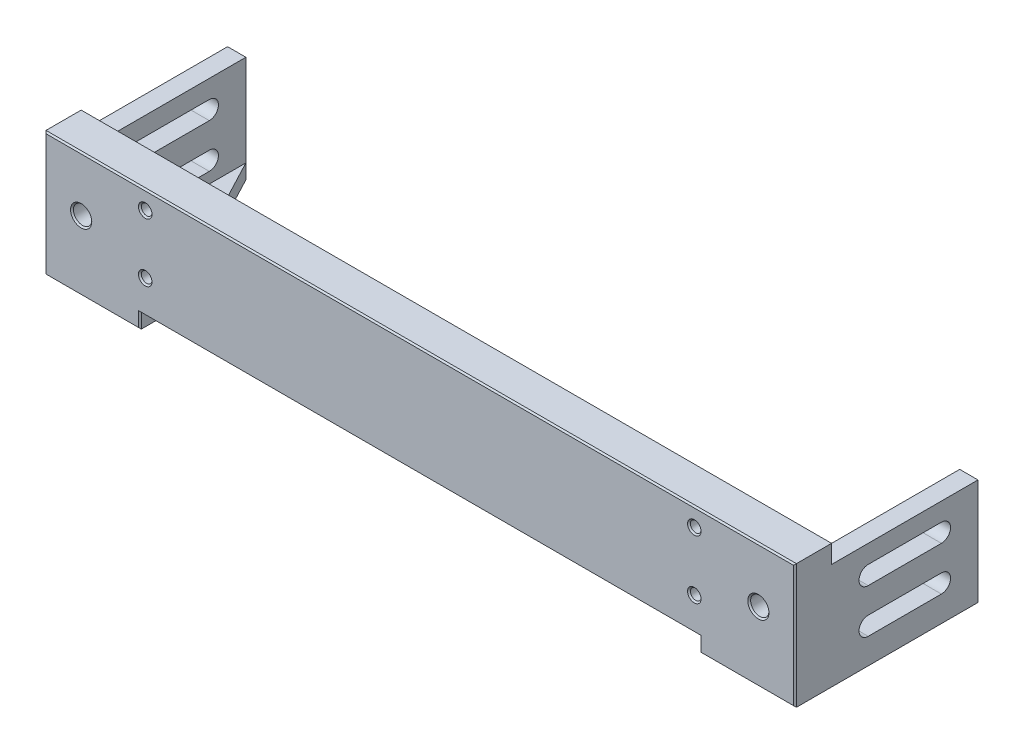
SolidWorks part; units mm, degrees
ref_plane "Front Plane" through (0, 0, 0) normal (0, 0, 1) x (1, 0, 0)
ref_plane "Top Plane" through (0, 0, 0) normal (0, 1, 0) x (1, 0, 0)
ref_plane "Right Plane" through (0, 0, 0) normal (1, 0, 0) x (0, 0, -1)
sketch "Sketch1" plane through (0, 0, 0) normal (0, 0, 1) x (1, 0, 0)
  line L0 (0, 0) -> (0, 19.05) construction
  line L1 (-130.175, 19.05) -> (130.175, 19.05)
  line L2 (-130.175, 19.05) -> (-130.175, -19.05)
  line L3 (-130.175, -19.05) -> (130.175, -19.05)
  line L4 (130.175, 19.05) -> (130.175, -19.05)
  line L5 (-130.175, 19.05) -> (130.175, -19.05) construction
  line L6 (-130.175, -19.05) -> (130.175, 19.05) construction
  line L7 (-81.28, 10.16) -> (-81.28, -10.16) construction
  line L8 (-81.28, 0) -> (-117.475, 0) construction
  circle A0 centre (-117.475, 0) radius 3.175
  circle A1 centre (117.475, 0) radius 3.175
  circle A7 centre (-95.25, 12.7) radius 1.85
  circle A8 centre (-95.25, -7.62) radius 1.85
  circle A9 centre (95.25, -7.62) radius 1.85
  circle A10 centre (95.25, 12.7) radius 1.85
  point P0 (0, 0)
  dimension "D1" = 6.35
  dimension "D6" = 20.32
  dimension "D9" = 3.7
  dimension "D10" = 190.5
  dimension "D2" = 260.35
  dimension "D3" = 12.7
  dimension "D4" = 38.1
  dimension "D5" = 20.32
  dimension "D7" = 81.28
  dimension "D8" = 12.7
extrude "Boss-Extrude1" add sketch "Sketch1" along normal blind 12.7
sketch "Sketch2" plane through (0, 0, 0) normal (0, 0, -1) x (-1, 0, 0)
  line L0 (-130.175, 12.7) -> (-130.175, -19.05)
  line L1 (-130.175, -19.05) -> (-123.825, -19.05)
  line L2 (130.175, -19.05) -> (-130.175, -19.05) construction
  line L3 (-123.825, -19.05) -> (-123.825, 12.7)
  line L5 (-123.825, 12.7) -> (-130.175, 12.7)
  point P4 (0, 0)
  point P9 (0, 0)
  point P10 (-123.825, 16.4813)
  point P11 (0, 0)
  dimension "D1" = 6.35
  dimension "D2" = 31.75
extrude "Boss-Extrude2" add sketch "Sketch2" along normal blind 50.8
sketch "Sketch3" plane through (123.825, 0, 0) normal (-1, 0, 0) x (0, 0, 1)
  line L0 (-38.1, 6.35) -> (-12.7, 6.35)
  line L1 (-25.4, 12.7) -> (-25.4, 6.35) construction
  line L2 (-38.1, 0) -> (-12.7, 0)
  line L3 (-50.8, 12.7) -> (0, 12.7) construction
  line L4 (-38.1, -8.89) -> (-12.7, -8.89)
  line L5 (-25.4, 6.35) -> (-25.4, -8.89) construction
  line L6 (-38.1, -15.24) -> (-12.7, -15.24)
  line L8 (12.7, -19.05) -> (-50.8, -19.05) construction
  arc A0 (-38.1, 6.35) -> (-38.1, 0) centre (-38.1, 3.175) ccw
  arc A1 (-38.1, -8.89) -> (-38.1, -15.24) centre (-38.1, -12.065) ccw
  arc A2 (-12.7, -15.24) -> (-12.7, -8.89) centre (-12.7, -12.065) ccw
  arc A3 (-12.7, 0) -> (-12.7, 6.35) centre (-12.7, 3.175) ccw
  point P5 (-37.6203, -18.3705)
  point P20 (-39.22, -12.7)
  point P21 (0, 0)
  dimension "D1" = 8.89
  dimension "D4" = 25.4
  dimension "D2" = 25.4
  dimension "D3" = 6.35
  dimension "D5" = 6.35
extrude "Cut-Extrude1" cut sketch "Sketch3" against normal blind 50.8
sketch "Sketch4" plane through (0, -19.05, 0) normal (0, -1, 0) x (-1, 0, 0)
  line L0 (-123.825, 50.8) -> (-97.1, 0)
  line L1 (-123.825, 50.8) -> (-130.175, 50.8)
  line L2 (-130.175, 50.8) -> (-130.175, -12.7)
  line L3 (-130.175, -12.7) -> (-97.1, -12.7)
  line L4 (130.175, -12.7) -> (-130.175, -12.7) construction
  line L5 (-97.1, -12.7) -> (-97.1, 0)
extrude "Boss-Extrude3" add sketch "Sketch4" along normal blind 5.08
mirror "Mirror1" about plane through (0, 0, 0) normal (1, 0, 0) of "Boss-Extrude1", "Boss-Extrude2", "Boss-Extrude3", "Cut-Extrude1"
chamfer "Chamfer1" distance 0.5 angle 45 14 edges at (93.4, 12.7, 12.7) (-93.4, 12.7, 12.7) (114.3, 0, 12.7) (-114.3, 0, 12.7) (-97.1, -7.62, 12.7) (97.1, -7.62, 12.7) (113.6375, -24.13, 12.7) (97.1, -21.59, 12.7) (0, -19.05, 12.7) (-97.1, -21.59, 12.7) (-113.6375, -24.13, 12.7) (-130.175, -2.54, 12.7) (0, 19.05, 12.7) (130.175, -2.54, 12.7)
